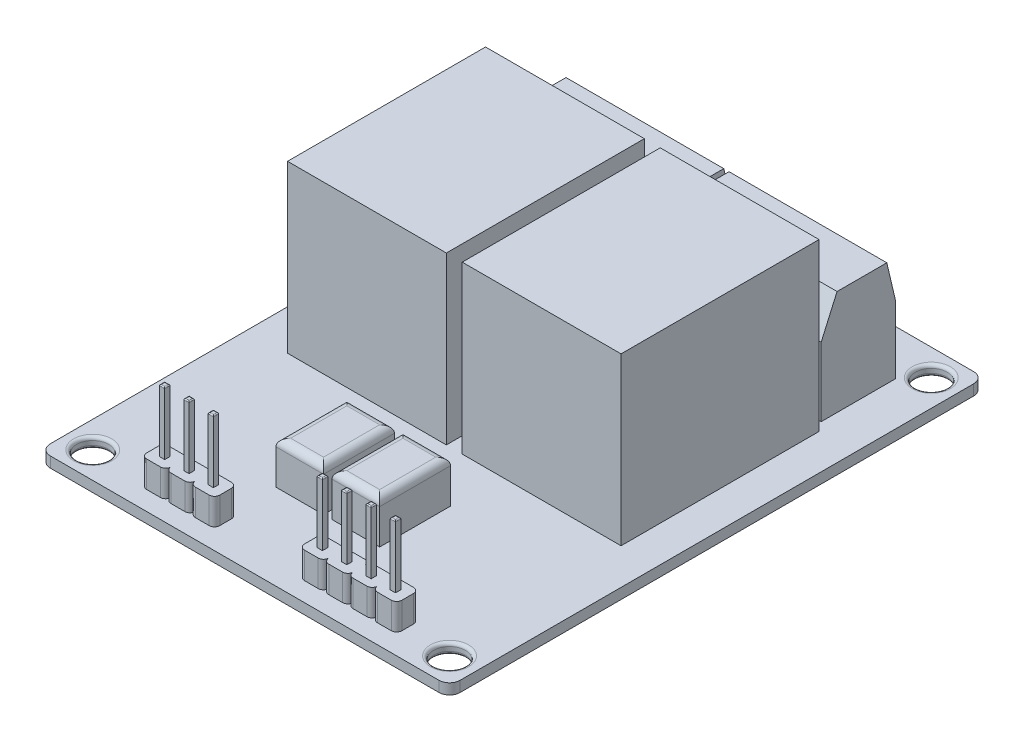
SolidWorks part; units mm, degrees
ref_plane "Alzado" through (0, 0, 0) normal (0, 0, 1) x (1, 0, 0)
ref_plane "Planta" through (0, 0, 0) normal (0, 1, 0) x (1, 0, 0)
ref_plane "Vista lateral" through (0, 0, 0) normal (1, 0, 0) x (0, 0, -1)
sketch "Croquis1" plane through (0, 0, 0) normal (0, 1, 0) x (1, 0, 0)
  line L1 (0, 0) -> (38.7, 0)
  line L2 (0, 0) -> (0, -50.5)
  line L3 (0, -50.5) -> (38.7, -50.5)
  line L4 (38.7, 0) -> (38.7, -50.5)
  dimension "D1" = 38.7
  dimension "D2" = 50.5
extrude "Saliente-Extruir1" add sketch "Croquis1" against normal blind 1
sketch "Croquis2" plane through (0, 0, 0) normal (0, 1, 0) x (1, 0, 0)
  line L0 (0, 0) -> (0, -50.5) construction
  line L1 (3.8, -12.2) -> (18.8, -12.2)
  line L2 (3.8, -12.2) -> (3.8, -30.9)
  line L3 (3.8, -30.9) -> (18.8, -30.9)
  line L4 (18.8, -12.2) -> (18.8, -30.9)
  line L5 (20.3, -12.2) -> (35.3, -12.2)
  line L6 (20.3, -12.2) -> (20.3, -30.9)
  line L7 (20.3, -30.9) -> (35.3, -30.9)
  line L8 (35.3, -12.2) -> (35.3, -30.9)
  line L10 (38.7, 0) -> (0, 0) construction
  dimension "D1" = 15
  dimension "D2" = 3.8
  dimension "D3" = 1.5
  dimension "D4" = 18.7
  dimension "D5" = 30.9
extrude "Saliente-Extruir2" add sketch "Croquis2" along normal blind 15.7
sketch "Croquis3" plane through (0, 0, 0) normal (0, 1, 0) x (1, 0, 0)
  line L0 (3.8, -12.2) -> (3.8, -30.9) construction
  line L1 (4.3, -4.3) -> (19.2, -4.3)
  line L2 (4.3, -4.3) -> (4.3, -11.3)
  line L3 (4.3, -11.3) -> (19.2, -11.3)
  line L4 (19.2, -4.3) -> (19.2, -11.3)
  line L5 (19.7, -4.3) -> (34.6, -4.3)
  line L6 (19.7, -4.3) -> (19.7, -11.3)
  line L7 (19.7, -11.3) -> (34.6, -11.3)
  line L8 (34.6, -4.3) -> (34.6, -11.3)
  line L9 (38.7, 0) -> (0, 0) construction
  dimension "D1" = 14.9
  dimension "D2" = 0.5
  dimension "D3" = 7
  dimension "D4" = 4.3
  dimension "D5" = 0.5
extrude "Saliente-Extruir3" add sketch "Croquis3" along normal blind 9.9
sketch "Croquis4" plane through (34.6, 0, 0) normal (1, 0, 0) x (0, 0, -1)
  line L0 (-11.3, 6.5) -> (-4.3, 6.5)
  line L1 (-11.3, 9.9) -> (-11.3, 0) construction
  line L2 (-4.3, 9.9) -> (-4.3, 0) construction
  line L3 (-11.3, 9.9) -> (-4.3, 9.9) construction
  line L4 (-9.8, 9.9) -> (-11.3, 6.5)
  line L5 (-11.3, 9.9) -> (-9.8, 9.9)
  line L6 (-4.3, 6.5) -> (-5.1, 9.9)
  line L7 (-5.1, 9.9) -> (-4.3, 9.9)
  line L8 (-4.3, 9.9) -> (-4.3, 6.5)
  line M2 (-4.3, 0) -> (-4.3, 9.9)
  line M3 (-4.3, 9.9) -> (-11.3, 9.9)
  line M4 (-11.3, 9.9) -> (-11.3, 0)
  dimension "D1" = 3.4
  dimension "D2" = 1.5
  dimension "D3" = 0.8
extrude "Cortar-Extruir1" cut sketch "Croquis4" against normal through all contours L4 M3 M4 | L6 M2 M3 region at (34.6, 8.7667, 10.8) region at (34.6, 8.7667, 4.5667)
sketch "Croquis5" plane through (0, 0, 0) normal (0, 1, 0) x (1, 0, 0)
  line L0 (3.8, -30.9) -> (18.8, -30.9) construction
  line L1 (14.2, -35.7) -> (18.7, -35.7)
  line L2 (14.2, -35.7) -> (14.2, -42.4)
  line L3 (14.2, -42.4) -> (18.7, -42.4)
  line L4 (18.7, -35.7) -> (18.7, -42.4)
  line L5 (19.5, -35.7) -> (24, -35.7)
  line L6 (19.5, -35.7) -> (19.5, -42.4)
  line L7 (19.5, -42.4) -> (24, -42.4)
  line L8 (24, -35.7) -> (24, -42.4)
  line L9 (0, 0) -> (0, -50.5) construction
  dimension "D1" = 4.5
  dimension "D2" = 6.7
  dimension "D3" = 4.8
  dimension "D4" = 14.2
  dimension "D5" = 0.8
extrude "Saliente-Extruir4" add sketch "Croquis5" along normal blind 4
fillet "Redondeo1" radius 0.7 8 edges at (19.5, 4, 39.05) (21.75, 4, 42.4) (24, 4, 39.05) (21.75, 4, 35.7) (16.45, 4, 35.7) (14.2, 4, 39.05) (16.45, 4, 42.4) (18.7, 4, 39.05)
sketch "Croquis6" plane through (0, 0, 0) normal (0, 1, 0) x (1, 0, 0)
  line L0 (29.6, -46.6) -> (27.3, -46.6)
  line L1 (31.9, -46.6) -> (29.6, -46.6)
  line L2 (31.9, -46.6) -> (31.9, -48.7)
  line L3 (31.9, -48.7) -> (29.6, -48.7)
  line L4 (29.6, -46.6) -> (29.6, -48.7)
  line L5 (29.6, -46.6) -> (29.6, -48.7)
  line L6 (29.6, -48.7) -> (27.3, -48.7)
  line L7 (27.3, -46.6) -> (27.3, -48.7)
  line L8 (27.3, -46.6) -> (25, -46.6)
  line L9 (27.3, -46.6) -> (27.3, -48.7)
  line L10 (27.3, -48.7) -> (25, -48.7)
  line L11 (25, -46.6) -> (25, -48.7)
  line L12 (25, -46.6) -> (22.7, -46.6)
  line L13 (25, -46.6) -> (25, -48.7)
  line L14 (25, -48.7) -> (22.7, -48.7)
  line L15 (22.7, -46.6) -> (22.7, -48.7)
  line L16 (38.7, -50.5) -> (38.7, 0) construction
  line L17 (0, -50.5) -> (38.7, -50.5) construction
  line L18 (14.7, -46.6) -> (12.4, -46.6)
  line L19 (14.7, -46.6) -> (14.7, -48.7)
  line L20 (14.7, -46.6) -> (14.7, -48.7)
  line L21 (14.7, -48.7) -> (12.4, -48.7)
  line L22 (12.4, -46.6) -> (12.4, -48.7)
  line L23 (12.4, -46.6) -> (10.1, -46.6)
  line L24 (12.4, -46.6) -> (12.4, -48.7)
  line L25 (12.4, -48.7) -> (10.1, -48.7)
  line L26 (10.1, -46.6) -> (10.1, -48.7)
  line L27 (10.1, -46.6) -> (7.8, -46.6)
  line L28 (10.1, -46.6) -> (10.1, -48.7)
  line L29 (10.1, -48.7) -> (7.8, -48.7)
  line L30 (7.8, -46.6) -> (7.8, -48.7)
  line L31 (0, 0) -> (0, -50.5) construction
  dimension "D1" = 2.1
  dimension "D2" = 2.3
  dimension "D3" = 6.8
  dimension "D4" = 1.8
  dimension "D5" = 7.8
extrude "Saliente-Extruir5" add sketch "Croquis6" along normal blind 2.5 contours L1 L4 L3 L2 region at (30.75, 0, 47.65)
fillet "Redondeo2" radius 0.5 4 edges at (29.6, 1.25, 48.7) (31.9, 1.25, 48.7) (31.9, 1.25, 46.6) (29.6, 1.25, 46.6)
extrude "Saliente-Extruir6" add sketch "Croquis6<3>" along normal blind 2.5 contours L0 L7 L6 L4 region at (28.45, 0, 47.65)
sketch "Croquis6<3>" plane through (0, 0, 0) normal (0, 1, 0) x (1, 0, 0) same geometry as "Croquis6"
fillet "Redondeo4" radius 0.5 4 edges at (27.3, 1.25, 48.7) (29.6, 1.25, 46.6) (27.3, 1.25, 46.6) (29.6, 1.25, 48.7)
extrude "Saliente-Extruir7" add sketch "Croquis6<4>" along normal blind 2.5 contours L8 L11 L10 L7 region at (26.15, 0, 47.65)
sketch "Croquis6<4>" plane through (0, 0, 0) normal (0, 1, 0) x (1, 0, 0) same geometry as "Croquis6"
fillet "Redondeo5" radius 0.5 4 edges at (27.3, 1.25, 46.6) (25, 1.25, 46.6) (25, 1.25, 48.7) (27.3, 1.25, 48.7)
extrude "Saliente-Extruir8" add sketch "Croquis6<5>" along normal blind 2.5 contours L12 L15 L14 L11 region at (23.85, 0, 47.65)
sketch "Croquis6<5>" plane through (0, 0, 0) normal (0, 1, 0) x (1, 0, 0) same geometry as "Croquis6"
fillet "Redondeo6" radius 0.5 4 edges at (25, 1.25, 46.6) (22.7, 1.25, 46.6) (22.7, 1.25, 48.7) (25, 1.25, 48.7)
extrude "Saliente-Extruir9" add sketch "Croquis6<6>" along normal blind 2.5 contours L18 L22 L21 L19 | L27 L30 L29 L26 region at (13.55, 0, 47.65) region at (8.95, 0, 47.65)
sketch "Croquis6<6>" plane through (0, 0, 0) normal (0, 1, 0) x (1, 0, 0) same geometry as "Croquis6"
fillet "Redondeo7" radius 0.5 8 edges at (7.8, 1.25, 46.6) (7.8, 1.25, 48.7) (10.1, 1.25, 48.7) (10.1, 1.25, 46.6) (12.4, 1.25, 46.6) (12.4, 1.25, 48.7) (14.7, 1.25, 48.7) (14.7, 1.25, 46.6)
extrude "Saliente-Extruir10" add sketch "Croquis6<7>" along normal blind 2.5 contours L23 L26 L25 L22 region at (11.25, 0, 47.65)
sketch "Croquis6<7>" plane through (0, 0, 0) normal (0, 1, 0) x (1, 0, 0) same geometry as "Croquis6"
fillet "Redondeo8" radius 0.5 4 edges at (10.1, 1.25, 46.6) (10.1, 1.25, 48.7) (12.4, 1.25, 48.7) (12.4, 1.25, 46.6)
sketch "Croquis8" plane through (0, 2.5, 0) normal (0, 1, 0) x (1, 0, 0)
  line L0 (7.8, -47.65) -> (14.7, -47.65) construction
  line L1 (7.8, -47.1) -> (7.8, -48.2) construction
  line L2 (14.7, -47.1) -> (14.7, -48.2) construction
  line L3 (22.7, -47.65) -> (31.9, -47.65) construction
  line L4 (22.7, -47.1) -> (22.7, -48.2) construction
  line L5 (31.9, -47.1) -> (31.9, -48.2) construction
  line L6 (23.85, -46.6) -> (23.85, -48.7) construction
  line L7 (24.5, -46.6) -> (23.2, -46.6) construction
  line L8 (24.5, -48.7) -> (23.2, -48.7) construction
  line L9 (26.15, -46.6) -> (26.15, -48.7) construction
  line L10 (26.8, -46.6) -> (25.5, -46.6) construction
  line L11 (26.8, -48.7) -> (25.5, -48.7) construction
  line L12 (28.45, -46.6) -> (28.45, -48.7) construction
  line L13 (29.1, -46.6) -> (27.8, -46.6) construction
  line L14 (29.1, -48.7) -> (27.8, -48.7) construction
  line L15 (30.75, -46.6) -> (30.75, -48.7) construction
  line L16 (31.4, -46.6) -> (30.1, -46.6) construction
  line L17 (31.4, -48.7) -> (30.1, -48.7) construction
  line L18 (13.55, -46.6) -> (13.55, -48.7) construction
  line L19 (14.2, -46.6) -> (12.9, -46.6) construction
  line L20 (14.2, -48.7) -> (12.9, -48.7) construction
  line L21 (11.25, -48.7) -> (11.25, -46.6) construction
  line L22 (11.9, -48.7) -> (10.6, -48.7) construction
  line L23 (11.9, -46.6) -> (10.6, -46.6) construction
  line L24 (8.95, -46.6) -> (8.95, -48.7) construction
  line L25 (9.6, -46.6) -> (8.3, -46.6) construction
  line L26 (9.6, -48.7) -> (8.3, -48.7) construction
  line L27 (11, -47.4) -> (11.5, -47.4)
  line L28 (8.7, -47.4) -> (9.2, -47.4)
  line L29 (8.7, -47.4) -> (8.7, -47.9)
  line L30 (8.7, -47.9) -> (9.2, -47.9)
  line L31 (9.2, -47.4) -> (9.2, -47.9)
  line L32 (11, -47.4) -> (11, -47.9)
  line L33 (11, -47.9) -> (11.5, -47.9)
  line L34 (11.5, -47.4) -> (11.5, -47.9)
  line L35 (13.3, -47.4) -> (13.8, -47.4)
  line L36 (13.3, -47.4) -> (13.3, -47.9)
  line L37 (13.3, -47.9) -> (13.8, -47.9)
  line L38 (13.8, -47.4) -> (13.8, -47.9)
  line L43 (23.6, -47.4) -> (24.1, -47.4)
  line L44 (23.6, -47.4) -> (23.6, -47.9)
  line L45 (23.6, -47.9) -> (24.1, -47.9)
  line L46 (24.1, -47.4) -> (24.1, -47.9)
  line L47 (25.9, -47.4) -> (26.4, -47.4)
  line L48 (25.9, -47.4) -> (25.9, -47.9)
  line L49 (25.9, -47.9) -> (26.4, -47.9)
  line L50 (26.4, -47.4) -> (26.4, -47.9)
  line L51 (28.2, -47.4) -> (28.7, -47.4)
  line L52 (28.2, -47.4) -> (28.2, -47.9)
  line L53 (28.2, -47.9) -> (28.7, -47.9)
  line L54 (28.7, -47.4) -> (28.7, -47.9)
  line L55 (30.5, -47.4) -> (31, -47.4)
  line L56 (30.5, -47.4) -> (30.5, -47.9)
  line L57 (30.5, -47.9) -> (31, -47.9)
  line L58 (31, -47.4) -> (31, -47.9)
  dimension "D1" = 0.5
  dimension "D2" = 0.25
  dimension "D3" = 0.25
  dimension "D4" = 0.25
  dimension "D5" = 0.25
  dimension "D6" = 0.25
  dimension "D7" = 0.25
  dimension "D8" = 0.25
  dimension "D9" = 0.25
extrude "Saliente-Extruir11" add sketch "Croquis8" along normal blind 5.9
fillet "Redondeo13" radius 0.1 28 edges at (30.5, 8.4, 47.65) (30.75, 8.4, 47.9) (31, 8.4, 47.65) (30.75, 8.4, 47.4) (28.2, 8.4, 47.65) (28.45, 8.4, 47.9) (28.7, 8.4, 47.65) (28.45, 8.4, 47.4) (25.9, 8.4, 47.65) (26.15, 8.4, 47.9) (26.4, 8.4, 47.65) (26.15, 8.4, 47.4) (24.1, 8.4, 47.65) (23.85, 8.4, 47.9) (23.6, 8.4, 47.65) (23.85, 8.4, 47.4) (13.3, 8.4, 47.65) (13.55, 8.4, 47.9) (13.8, 8.4, 47.65) (13.55, 8.4, 47.4) (11.25, 8.4, 47.9) (11, 8.4, 47.65) (11.5, 8.4, 47.65) (11.25, 8.4, 47.4) (8.95, 8.4, 47.4) (8.7, 8.4, 47.65) (8.95, 8.4, 47.9) (9.2, 8.4, 47.65)
fillet "Redondeo14" radius 1 2 edges at (38.7, -0.5, 50.5) (0, -0.5, 50.5)
fillet "Redondeo15" radius 1 2 edges at (0, -0.5, 0) (38.7, -0.5, 0)
sketch "Croquis9" plane through (0, 0, 0) normal (0, 1, 0) x (1, 0, 0)
  line L0 (37.7, 0) -> (1, 0) construction
  line L1 (0, -1) -> (0, -49.5) construction
  line L2 (38.7, -49.5) -> (38.7, -1) construction
  line L3 (1, -50.5) -> (37.7, -50.5) construction
  circle A0 centre (2.5, -2.5) radius 1.5
  circle A1 centre (36.2, -2.5) radius 1.5
  circle A2 centre (36.2, -48) radius 1.5
  circle A3 centre (2.5, -48) radius 1.5
  dimension "D1" = 3
  dimension "D5" = 2.5
  dimension "D2" = 2.5
  dimension "D3" = 2.5
  dimension "D4" = 2.5
extrude "Cortar-Extruir2" cut sketch "Croquis9" against normal blind 5.9
fillet "Redondeo16" radius 0.3 8 edges at (36.2, -1, 4) (36.2, -1, 49.5) (2.5, -1, 49.5) (2.5, -1, 4) (2.5, 0, 4) (36.2, 0, 4) (2.5, 0, 49.5) (36.2, 0, 49.5)
